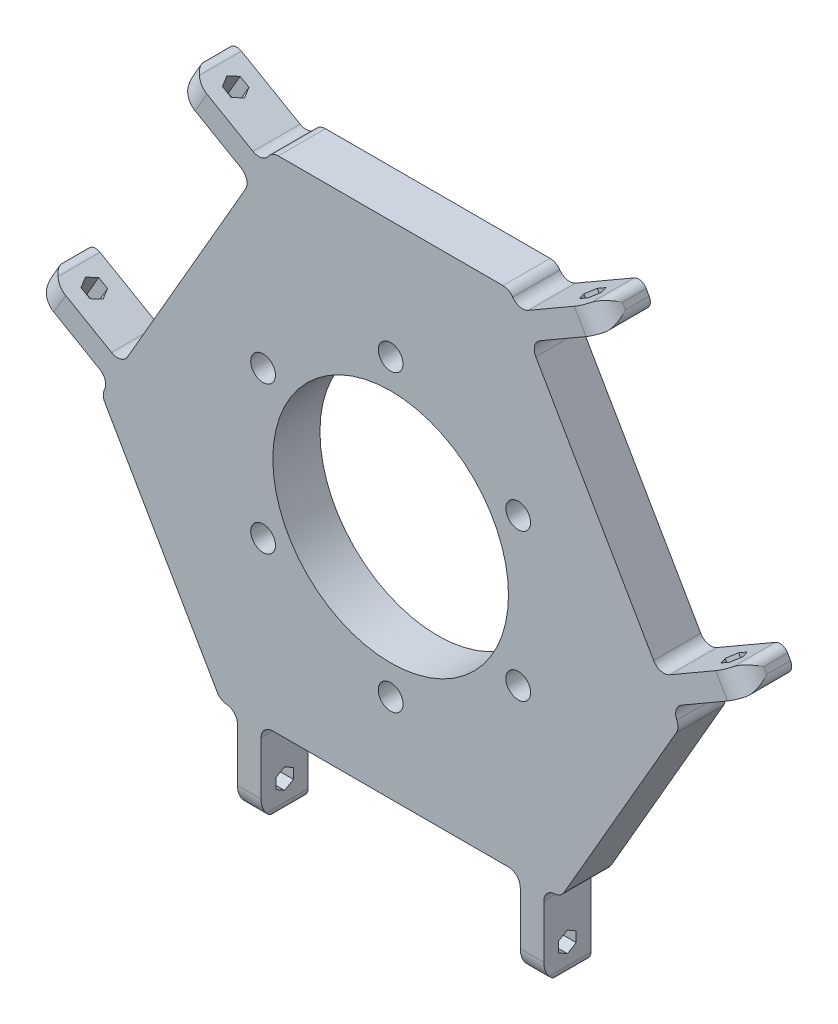
SolidWorks part; units mm, degrees
note: '?' marks a value the reader was unsure of.
ref_plane "Front Plane" through (0, 0, 0) normal (0, 0, 1) x (1, 0, 0)
ref_plane "Top Plane" through (0, 0, 0) normal (0, 1, 0) x (1, 0, 0)
ref_plane "Right Plane" through (0, 0, 0) normal (1, 0, 0) x (0, 0, -1)
sketch "Sketch1" plane through (0, 0, 0) normal (0, 0, 1) x (1, 0, 0)
  line L0 (49.0748, -5) -> (20.2073, 45)
  line L1 (-28.8675, -40) -> (28.8675, -40)
  line L2 (-20.2073, 45) -> (-49.0748, -5)
  line L3 (20.2073, 45) -> (-20.2073, 45)
  line L4 (-28.8675, -40) -> (-49.0748, -5)
  line L6 (49.0748, -5) -> (28.8675, -40)
  circle A0 centre (0, 0) radius 20
  dimension "D1" = 40
  dimension "D2" = 40
  dimension "D3" = 40
  dimension "D4" = 45
  dimension "D5" = 40
  dimension "D6" = 45
  dimension "D7" = 45
extrude "Boss-Extrude1" add sketch "Sketch1" along normal blind 8
sketch "Sketch3" plane through (0, 0, 0) normal (1, 0, 0) x (0, 0, -1)
  line L0 (0, -40) -> (0, -55)
  line L1 (0, -55) -> (-4, -55)
  line L2 (-8, -51) -> (-8, -40)
  line L3 (-8, -40) -> (0, -40)
  line L4 (-8, -40) -> (0, -40) construction
  line L5 (-4, -48.2679) -> (-5.5, -49.134)
  line L6 (-5.5, -49.134) -> (-5.5, -50.866)
  line L7 (-5.5, -50.866) -> (-4, -51.7321)
  line L8 (-4, -51.7321) -> (-2.5, -50.866)
  line L9 (-2.5, -50.866) -> (-2.5, -49.134)
  line L10 (-2.5, -49.134) -> (-4, -48.2679)
  circle A0 centre (-4, -50) radius 1.5 construction
  arc A1 (-4, -55) -> (-8, -51) centre (-4, -51) cw
  dimension "D1" = 4
  dimension "D3" = 3
  dimension "D2" = 15
  dimension "D4" = 5
  dimension "D5" = 4
extrude "Boss-Extrude3" add sketch "Sketch3" along normal blind 4 from offset 22
mirror "Mirror1" about plane through (0, 0, 0) normal (1, 0, 0) of "Boss-Extrude3"
ref_axis "Axis1" through (-38.7506, -50, 4) along (1, 0, 0)?
pattern_circular "CirPattern1" count 3 over 360 about axis through (0, 0, 0) along (0, 0, 1) of "Mirror1", "Boss-Extrude3"
sketch "Sketch4" plane through (0, 0, 8) normal (0, 0, 1) x (1, 0, 0)
  circle A0 centre (0, 25) radius 2.1
  dimension "D1" = 4.2
  dimension "D2" = 25
extrude "Cut-Extrude1" cut sketch "Sketch4" against normal through all
pattern_circular "CirPattern2" count 6 over 360 about axis through (0, 0, 0) along (0, 0, 1) of "Cut-Extrude1"
fillet "Fillet2" radius 2 12 edges at (-26, -40, 4) (-22, -40, 4) (-47.641, -2.5167, 4) (-45.641, 0.9474, 4) (23.641, 39.0526, 4) (21.641, 42.5167, 4)
fillet "Fillet4" radius 1.5 12 edges at (36.6314, 46.5526, 2) (34.6314, 50.0167, 2) (58.6314, 8.4474, 2) (60.6314, 4.9833, 2) (-60.6314, 4.9833, 2) (-58.6314, 8.4474, 2) (-36.6314, 46.5526, 2) (-34.6314, 50.0167, 2) (26, -55, 2) (22, -55, 2) (-26, -55, 2) (-22, -55, 2)
sketch "Sketch6" plane through (13, 22.5167, 0) normal (0.5, 0.866, 0) x (-0.866, 0.5, 0)
  line L0 (48.2679, 4) -> (51.7321, 4) construction
  line L1 (51.7321, 4) -> (50.866, 2.5) construction
  line L2 (50.866, 5.5) -> (51.7321, 4) construction
  point P7 (50, 4)
ref_axis "Axis2" through (-59.0695, -2.3114, 4) along (0.5, 0.866, 0)?
sketch "Sketch7" plane through (13, -22.5167, 0) normal (0.5, -0.866, 0) x (0, 0, -1)
  line L0 (-4, 48.2679) -> (-4, 51.7321) construction
  line L1 (-5.5, 50.866) -> (-4, 51.7321) construction
  point P5 (-4, 50)
ref_axis "Axis3" through (26.2689, 54.5009, 4) along (0.5, -0.866, 0)?
fillet "Fillet5" radius 2 6 edges at (20.2073, 45, 4) (-20.2073, 45, 4) (-49.0748, -5, 4) (-28.8675, -40, 4) (49.0748, -5, 4) (28.8675, -40, 4)
